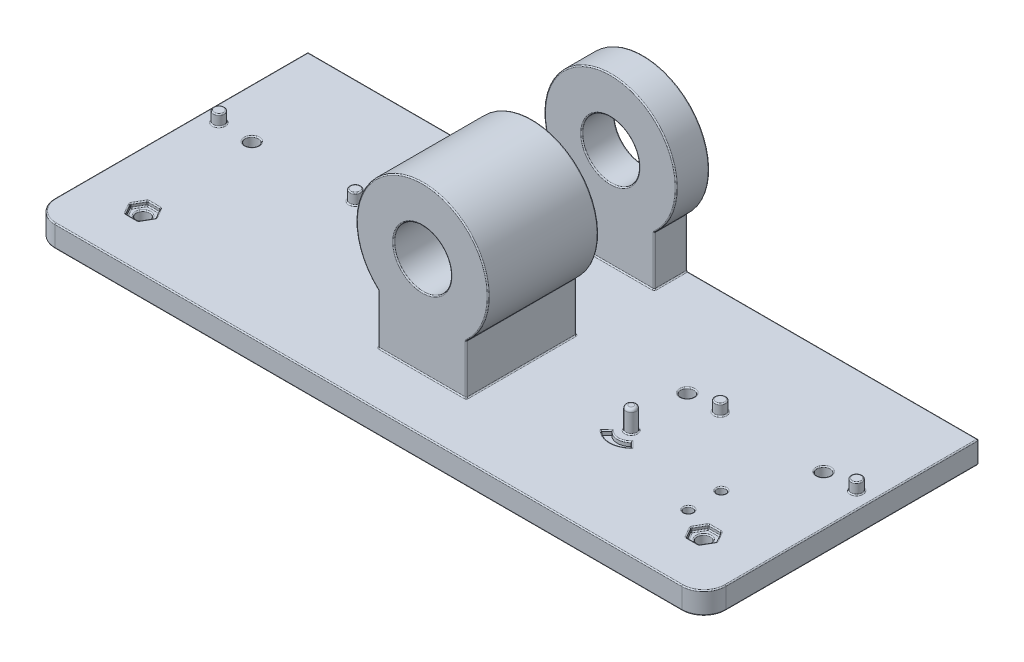
SolidWorks part; units mm, degrees
ref_plane "Front Plane" through (0, 0, 0) normal (0, 0, 1) x (1, 0, 0)
ref_plane "Top Plane" through (0, 0, 0) normal (0, 1, 0) x (1, 0, 0)
ref_plane "Right Plane" through (0, 0, 0) normal (1, 0, 0) x (0, 0, -1)
sketch "Sketch1" plane through (0, 0, 0) normal (0, 1, 0) x (1, 0, 0)
  line L0 (152.5, 125) -> (152.5, 0) construction
  line L1 (0, 0) -> (305, 0)
  line L2 (0, 0) -> (0, 125)
  line L3 (0, 125) -> (305, 125)
  line L4 (305, 0) -> (305, 125)
  line L5 (25, 100) -> (280, 100) construction
  line L6 (280, 25) -> (280, 100) construction
  line L7 (25, 25) -> (280, 25) construction
  line L8 (25, 25) -> (25, 100) construction
  line L9 (152.5, 62.5) -> (25, 62.5) construction
  line L10 (30.7735, 100) -> (27.8868, 105) construction
  line L11 (27.8868, 105) -> (22.1132, 105) construction
  line L12 (22.1132, 105) -> (19.2265, 100) construction
  line L13 (19.2265, 100) -> (22.1132, 95) construction
  line L14 (22.1132, 95) -> (27.8868, 95) construction
  line L15 (27.8868, 95) -> (30.7735, 100) construction
  line L16 (27.8868, 30) -> (30.7735, 25) construction
  line L17 (22.1132, 30) -> (27.8868, 30) construction
  line L18 (19.2265, 25) -> (22.1132, 30) construction
  line L19 (22.1132, 20) -> (19.2265, 25) construction
  line L20 (27.8868, 20) -> (22.1132, 20) construction
  line L21 (30.7735, 25) -> (27.8868, 20) construction
  line L22 (282.8868, 30) -> (277.1132, 30) construction
  line L23 (285.7735, 25) -> (282.8868, 30) construction
  line L24 (282.8868, 20) -> (285.7735, 25) construction
  line L25 (277.1132, 20) -> (282.8868, 20) construction
  line L26 (274.2265, 25) -> (277.1132, 20) construction
  line L27 (277.1132, 30) -> (274.2265, 25) construction
  line L28 (277.1132, 95) -> (274.2265, 100) construction
  line L29 (282.8868, 95) -> (277.1132, 95) construction
  line L30 (285.7735, 100) -> (282.8868, 95) construction
  line L31 (282.8868, 105) -> (285.7735, 100) construction
  line L32 (277.1132, 105) -> (282.8868, 105) construction
  line L33 (274.2265, 100) -> (277.1132, 105) construction
  line L34 (172.5, 75) -> (172.5, 125) construction
  line L35 (132.5, 0) -> (172.5, 0) construction
  line L36 (132.5, 0) -> (132.5, 125) construction
  line L37 (132.5, 125) -> (172.5, 125) construction
  line L38 (172.5, 0) -> (172.5, 125) construction
  line L39 (132.5, 75) -> (172.5, 75) construction
  line L40 (132.5, 75) -> (132.5, 25) construction
  line L41 (132.5, 25) -> (172.5, 25) construction
  line L42 (172.5, 75) -> (172.5, 25) construction
  line L50 (305, 14.5) -> (253.3, 14.5) construction
  line L51 (0, 84.5) -> (15, 69.5) construction
  line L52 (132.5, 75) -> (117.5, 60) construction
  line L53 (117.5, 60) -> (117.5, 85) construction
  line L54 (0, 125) -> (108, 125) construction
  line L55 (0, 125) -> (0, 84.5) construction
  line L56 (0, 84.5) -> (108, 84.5) construction
  line L57 (108, 125) -> (108, 84.5) construction
  line L58 (15, 69.5) -> (15, 84.5) construction
  line L59 (30, 84.5) -> (0, 84.5) construction
  line L60 (30, 84.5) -> (30, 69.5) construction
  line L61 (30, 69.5) -> (0, 69.5) construction
  line L62 (0, 84.5) -> (0, 69.5) construction
  line L63 (92, 84.5) -> (92, 69.5) construction
  line L64 (62, 0) -> (62, 125) construction
  line L65 (253.3, 14.5) -> (253.3, 0) construction
  line L66 (253.3, 38.75) -> (280.2, 38.75) construction
  line L67 (253.3, 14.5) -> (280.2, 14.5) construction
  line L68 (253.3, 14.5) -> (253.3, 63) construction
  line L69 (253.3, 63) -> (280.2, 63) construction
  line L70 (280.2, 14.5) -> (280.2, 63) construction
  line L71 (266.75, 31.25) -> (266.75, 38.75) construction
  circle A1 centre (25, 100) radius 5 construction
  circle A3 centre (280, 25) radius 3
  circle A4 centre (25, 25) radius 3
  circle A8 centre (117.5, 60) radius 3
  circle A9 centre (117.5, 85) radius 3
  circle A10 centre (7.5, 77) radius 3 construction
  circle A11 centre (22.5, 77) radius 3
  circle A12 centre (69.5, 77) radius 3 construction
  circle A13 centre (84.5, 77) radius 3
  circle A14 centre (220.5, 77) radius 3
  circle A15 centre (235.5, 77) radius 3 construction
  circle A16 centre (282.5, 77) radius 3
  circle A17 centre (297.5, 77) radius 3 construction
  circle A18 centre (266.75, 31.25) radius 2
  circle A19 centre (266.75, 46.25) radius 2
  dimension "D3" = 6
  dimension "D22" = 4
  dimension "D1" = 305
  dimension "D2" = 125
  dimension "D5" = 10
  dimension "D6" = 40
  dimension "D8" = 50
  dimension "D12" = 15
  dimension "D7" = 40.5
  dimension "D9" = 108
  dimension "D10" = 15
  dimension "D11" = 30
  dimension "D15" = 62
  dimension "D16" = 15
  dimension "D17" = 25
  dimension "D18" = 51.7
  dimension "D19" = 14.5
  dimension "D20" = 26.9
  dimension "D21" = 48.5
  dimension "D23" = 7.5
  dimension "D4" = 25
  dimension "D13" = 2
  dimension "D14" = 2
extrude "Boss-Extrude1" add sketch "Sketch1" along normal blind 10
sketch "Sketch7" plane through (0, 10, 0) normal (0, 1, 0) x (1, 0, 0)
  line L0 (0, 0) -> (305, 0) construction
  line L1 (132.5, 24.5) -> (172.5, 24.5)
  line L2 (132.5, 24.5) -> (132.5, 74.5)
  line L3 (132.5, 74.5) -> (172.5, 74.5)
  line L4 (172.5, 24.5) -> (172.5, 74.5)
  line L5 (152.5, 0) -> (152.5, 125) construction
  line L6 (305, 125) -> (0, 125) construction
  line L18 (132.5, 110) -> (172.5, 110)
  line L19 (132.5, 110) -> (132.5, 125)
  line L20 (132.5, 125) -> (172.5, 125)
  line L21 (172.5, 110) -> (172.5, 125)
  point P11 (152.5, 74.5)
  point P20 (152.5, 110)
  dimension "D1" = 40
  dimension "D2" = 50
  dimension "D4" = 15
  dimension "D3" = 35.5
extrude "Boss-Extrude2" add sketch "Sketch7" along normal blind 22.6393
sketch "Sketch11" plane through (0, 0, -24.5) normal (0, 0, 1) x (1, 0, 0)
  circle A0 centre (152.5, 55) radius 30
  circle A1 centre (152.5, 55) radius 13
  dimension "D1" = 60
  dimension "D2" = 26
extrude "Boss-Extrude3" add sketch "Sketch11" against normal up to surface (100.5 mm away) up to face at (152.5, 13.1598, -125)
ref_plane "Plane1" through (0, 0, -62.5) normal (0, 0, 1) x (1, 0, 0)
sketch "Sketch12" plane through (305, 0, 0) normal (1, 0, 0) x (0, 0, -1)
  line L0 (125, 85) -> (24.5, 85) construction
  line L1 (74.5, 10) -> (110, 10)
  line L2 (74.5, 10) -> (74.5, 85)
  line L3 (74.5, 85) -> (110, 85)
  line L4 (110, 10) -> (110, 85)
  line L6 (110, 32.6393) -> (110, 10) construction
extrude "Cut-Extrude2" cut sketch "Sketch12" against normal through all
sketch "Sketch13" plane through (0, 10, 0) normal (0, 1, 0) x (1, 0, 0)
  line L0 (222.5, 49.5) -> (172.5, 49.5) construction
  line L1 (172.5, 24.5) -> (172.5, 74.5) construction
  circle A1 centre (222.5, 49.5) radius 2.4
  dimension "D1" = 4.8
  dimension "D2" = 50
extrude "Boss-Extrude4" add sketch "Sketch13" along normal blind 10
sketch "Sketch6" plane through (0, 10, 0) normal (0, 1, 0) x (1, 0, 0)
  line L0 (152.5, 125) -> (152.5, 0) construction
  line L7 (215.7825, 42.7825) -> (218.0806, 45.0806)
  line L8 (0, 0) -> (305, 0) construction
  line L9 (152.5, 62.5) -> (0, 62.5) construction
  line L10 (0, 125) -> (0, 0) construction
  line L29 (27.8868, 30) -> (30.7735, 25)
  line L30 (274.2265, 25) -> (277.1132, 20)
  line L31 (277.1132, 20) -> (282.8868, 20)
  line L32 (282.8868, 20) -> (285.7735, 25)
  line L33 (285.7735, 25) -> (282.8868, 30)
  line L34 (282.8868, 30) -> (277.1132, 30)
  line L35 (277.1132, 30) -> (274.2265, 25)
  line L36 (22.1132, 30) -> (27.8868, 30)
  line L37 (19.2265, 25) -> (22.1132, 30)
  line L38 (22.1132, 20) -> (19.2265, 25)
  line L39 (27.8868, 20) -> (22.1132, 20)
  line L40 (30.7735, 25) -> (27.8868, 20)
  line L41 (231.3388, 40.6612) -> (213.6612, 58.3388) construction
  line L42 (213.6612, 40.6612) -> (231.3388, 58.3388) construction
  line L43 (222.5, 49.5) -> (222.5, 37) construction
  line L44 (213.6612, 40.6612) -> (222.5, 37) construction
  line L45 (222.5, 37) -> (231.3388, 40.6612) construction
  line L46 (229.2175, 42.7825) -> (226.9194, 45.0806)
  circle A0 centre (280, 25) radius 5 construction
  circle A1 centre (222.5, 49.5) radius 12.5 construction
  circle A2 centre (222.5, 49.5) radius 9.5 construction
  circle A3 centre (222.5, 49.5) radius 6.25 construction
  arc A4 (218.0806, 45.0806) -> (226.9194, 45.0806) centre (222.5, 49.5) ccw
  arc A5 (215.7825, 42.7825) -> (229.2175, 42.7825) centre (222.5, 49.5) ccw
  dimension "D2" = 25
  dimension "D4" = 12.5
  dimension "D1" = 10
  dimension "D3" = 3
extrude "Cut-Extrude1" cut sketch "Sketch6" against normal blind 2
fillet "Fillet1" radius 1.3 1 edges at (222.5, 20, -47.1)
sketch "Sketch15" plane through (0, 10, 0) normal (0, 1, 0) x (1, 0, 0)
  line L0 (69.5, 77) -> (7.5, 77) construction
  line L1 (38.5, 77) -> (38.5, 84.5) construction
  line L2 (0, 84.5) -> (108, 84.5) construction
  line L3 (152.5, 125) -> (152.5, 0) construction
  circle A1 centre (69.5, 77) radius 2.5
  circle A2 centre (7.5, 77) radius 2.5
  circle A3 centre (7.5, 77) radius 2.5
  circle A4 centre (235.5, 77) radius 2.5
  circle A5 centre (297.5, 77) radius 2.5
  dimension "D1" = 0.5
extrude "Boss-Extrude5" add sketch "Sketch15" along normal blind 5
chamfer "Chamfer1" distance 3.3 angle 45 6 edges at (282.5, 0, -74) (220.5, 0, -74) (84.5, 0, -80) (22.5, 0, -80) (117.5, 0, -57) (117.5, 0, -82)
fillet "Fillet2" radius 0.5 99 edges at (25, 0, -28) (19.2265, 9, -25) (22.1132, 9, -20) (27.8868, 9, -30) (22.1132, 9, -30) (27.8868, 9, -20) (30.7735, 9, -25) (29.3301, 8, -27.5) (29.3301, 8, -22.5) (25, 8, -20) (20.6699, 8, -22.5) (20.6699, 8, -27.5) (25, 8, -30) (25, 8, -28) (280, 0, -22) (277.1132, 9, -30) (274.2265, 9, -25) (285.7735, 9, -25) (282.8868, 9, -30) (277.1132, 9, -20) (282.8868, 9, -20) (280, 8, -30) (284.3301, 8, -27.5) (284.3301, 8, -22.5) (280, 8, -20) (275.6699, 8, -22.5) (275.6699, 8, -27.5) (280, 8, -22) (235.5, 15, -74.5) (297.5, 15, -79.5) (69.5, 15, -79.5) (7.5, 15, -74.5) (117.5, 10, -57) (280, 10, -20) (284.3301, 10, -22.5) (284.3301, 10, -27.5) (280, 10, -30) (275.6699, 10, -27.5) (275.6699, 10, -22.5) (20.6699, 10, -22.5) (25, 10, -20) (29.3301, 10, -22.5) (29.3301, 10, -27.5) (25, 10, -30) (20.6699, 10, -27.5) (117.5, 10, -82) (305, 10, -62.5) (152.5, 10, 0) (0, 10, -62.5) (22.5, 10, -80) (84.5, 10, -80) (220.5, 10, -74) (282.5, 10, -74) (222.5, 10, -51.9) (7.5, 10, -79.5) (69.5, 10, -79.5) (235.5, 10, -79.5) (297.5, 10, -79.5) (165.5, 55, -24.5) (152.5, 10, -24.5) (152.5, 85, -24.5) (132.5, 32.6393, -49.5) (132.5, 21.3197, -24.5) (132.5, 10, -49.5) (165.5, 55, -74.5) (152.5, 10, -74.5) (152.5, 85, -74.5) (132.5, 21.3197, -74.5) (172.5, 21.3197, -24.5) (172.5, 32.6393, -49.5) (172.5, 21.3197, -74.5) (172.5, 10, -49.5) (172.5, 32.6393, -117.5) (172.5, 10, -117.5) (132.5, 32.6393, -117.5) (132.5, 10, -117.5) (165.5, 55, -125) (66.25, 10, -125) (0, 5, -125) (152.5, 0, -125) (305, 5, -125) (238.75, 10, -125) (172.5, 21.3197, -125) (152.5, 85, -125) (132.5, 21.3197, -125) (139.5, 55, -110) (152.5, 10, -110) (132.5, 21.3197, -110) (152.5, 85, -110) (172.5, 21.3197, -110) (305, 0, -62.5) (152.5, 0, 0) (0, 0, -62.5) (222.5, 10, -43.25) (216.9315, 10, -43.9315) (222.5, 10, -40) (228.0685, 10, -43.9315) (266.75, 10, -48.25) (266.75, 10, -29.25)
fillet "Fillet3" radius 10 6 edges at (0.1464, 0.1464, -0.1464) (0.1464, 9.8536, -0.1464) (304.8536, 0.1464, -0.1464) (304.8536, 9.8536, -0.1464) (305, 5, 0) (0, 5, 0)
equation "\"joint_width\"=4"
equation "\"short_base_length\"=12.5"
equation "\"D2@Sketch1\"=\"short_base_length\""
equation "\"outer_diam_main_joint\"=6"
equation "\"D1@Sketch11\"=\"outer_diam_main_joint\""
equation "\"D1@Sketch7\"=\"outer_diam_main_joint\"-2"
equation "\"D1@Boss-Extrude2\"=(\"outer_diam_main_joint\"/2)+1.5cm-sqr((\"outer_diam_main_joint\"/2)^2-((\"outer_diam_main_joint\"-2)/2)^2)"
equation "\"D6@Sketch1\"=\"outer_diam_main_joint\"-2"
equation "\"pulleyside\"=1.5"
